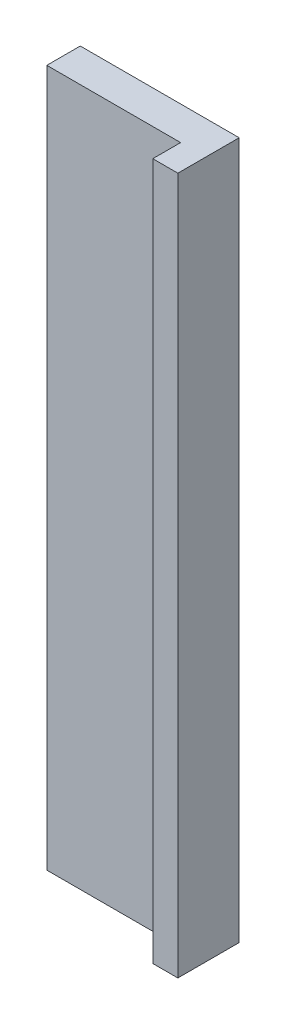
SolidWorks part; units mm, degrees
ref_plane "Alzado" through (0, 0, 0) normal (0, 0, 1) x (1, 0, 0)
ref_plane "Planta" through (0, 0, 0) normal (0, 1, 0) x (1, 0, 0)
ref_plane "Vista lateral" through (0, 0, 0) normal (1, 0, 0) x (0, 0, -1)
sketch "Croquis1" plane through (0, 0, 0) normal (0, 0, 1) x (1, 0, 0)
  line L1 (0, 0) -> (28.5, 0)
  line L2 (0, 0) -> (0, 125)
  line L3 (0, 125) -> (28.5, 125)
  line L4 (28.5, 0) -> (28.5, 125)
  dimension "D1" = 28.5
  dimension "D2" = 125
extrude "Saliente-Extruir1" add sketch "Croquis1" along normal blind 6
sketch "Croquis2" plane through (0, 0, 6) normal (0, 0, 1) x (1, 0, 0)
  line L0 (28.5, 125) -> (0, 125) construction
  line L1 (28.5, 0) -> (24, 0)
  line L2 (28.5, 0) -> (28.5, 125)
  line L3 (28.5, 125) -> (24, 125)
  line L4 (24, 0) -> (24, 125)
  dimension "D1" = 4.5
extrude "Saliente-Extruir2" add sketch "Croquis2" along normal blind 5
